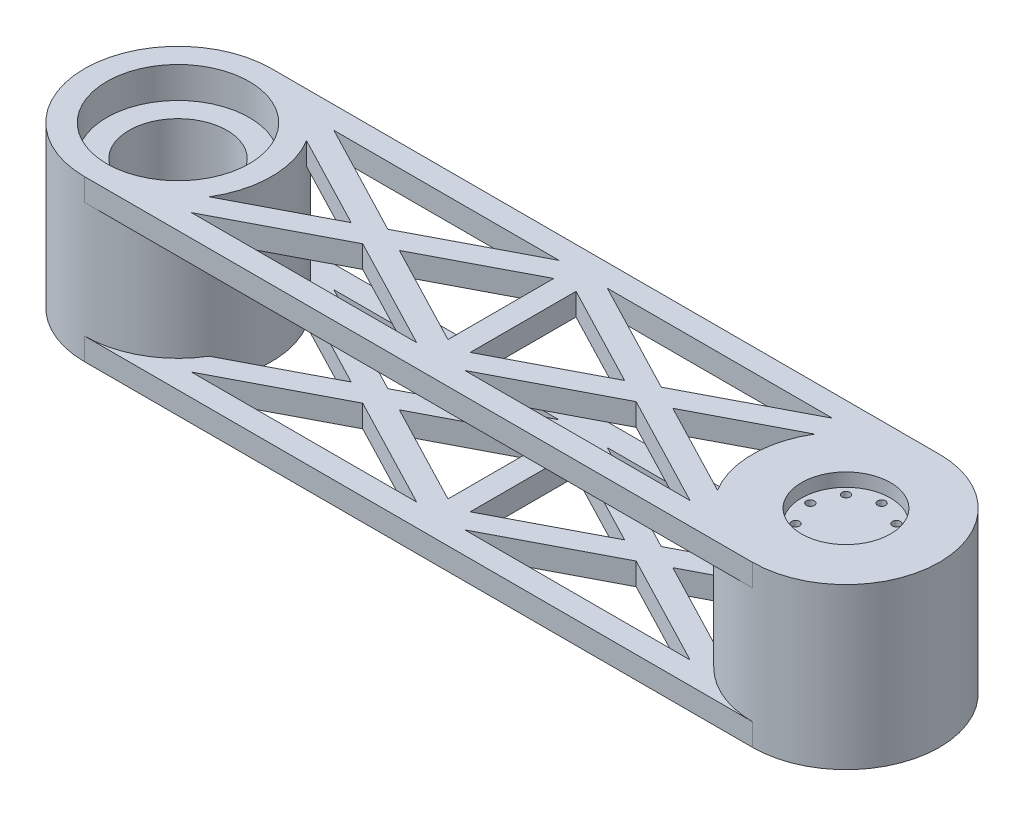
SolidWorks part; units mm, degrees
ref_plane "정면" through (0, 0, 0) normal (0, 0, 1) x (1, 0, 0)
ref_plane "윗면" through (0, 0, 0) normal (0, 1, 0) x (1, 0, 0)
ref_plane "우측면" through (0, 0, 0) normal (1, 0, 0) x (0, 0, -1)
sketch "스케치1" plane through (0, 0, 0) normal (0, 1, 0) x (1, 0, 0)
  circle A0 centre (68.9106, -5.2941) radius 21
  circle A1 centre (-81.0894, -5.2941) radius 21
  circle A2 centre (-81.0894, -5.2941) radius 16
  circle A3 centre (68.9106, -5.2941) radius 10
  dimension "D1" = 42
  dimension "D2" = 42
  dimension "D5" = 32
  dimension "D6" = 20
  dimension "D3" = 150
  dimension "D4" = 0
extrude "보스-돌출1" add sketch "스케치1" along normal blind 36
sketch "스케치2" plane through (0, 36, 0) normal (0, 1, 0) x (1, 0, 0)
  line L0 (-81.0894, -26.2941) -> (68.9106, -26.2941)
  line L1 (-81.0894, 15.7059) -> (68.9106, 15.7059)
  line L2 (-81.0894, -21.2941) -> (68.9106, -21.2941)
  line L3 (-81.0894, 10.7059) -> (68.9106, 10.7059)
  line L4 (-81.0894, -26.2941) -> (-81.0894, -21.2941)
  line L5 (68.9106, -26.2941) -> (68.9106, -21.2941)
  line L6 (68.9106, 10.7059) -> (68.9106, 15.7059)
  line L7 (-81.0894, 10.7059) -> (-81.0894, 15.7059)
  circle A1 centre (-81.0894, -5.2941) radius 21 construction
  circle A3 centre (68.9106, -5.2941) radius 21 construction
  circle A4 centre (-81.0894, -5.2941) radius 16 construction
  dimension "D1" = 21
  dimension "D2" = 21
  dimension "D3" = 5
  dimension "D4" = 5
extrude "보스-돌출3" add sketch "스케치2" against normal blind 5
sketch "스케치3" plane through (0, 0, 0) normal (0, -1, 0) x (1, 0, 0)
  line L0 (68.9106, -15.7059) -> (-81.0894, -15.7059)
  line L1 (68.9106, 26.2941) -> (-81.0894, 26.2941)
  line L2 (68.9106, 26.2941) -> (68.9106, 21.2941)
  line L3 (68.9106, -10.7059) -> (68.9106, -15.7059)
  line L4 (68.9106, 21.2941) -> (-81.0894, 21.2941)
  line L6 (-81.0894, -10.7059) -> (68.9106, -10.7059)
  line L7 (-81.0894, 26.2941) -> (-81.0894, 21.2941)
  line L8 (-81.0894, -10.7059) -> (-81.0894, -15.7059)
  circle A0 centre (68.9106, 5.2941) radius 21 construction
  circle A1 centre (-81.0894, 5.2941) radius 21 construction
  circle A3 centre (-81.0894, 5.2941) radius 16 construction
extrude "보스-돌출4" add sketch "스케치3" against normal blind 5
sketch "스케치4" plane through (0, 0, 0) normal (0, -1, 0) x (1, 0, 0)
  line L0 (-6.0894, 21.2941) -> (-6.0894, -10.7059) construction
  line L1 (-67.488, 21.2941) -> (55.3091, 21.2941) construction
  line L2 (55.3091, -10.7059) -> (-67.488, -10.7059) construction
  line L3 (-6.0894, -10.7059) -> (55.3091, 21.2941) construction
  line L4 (-36.7887, 8.1132) -> (-7.2449, 23.511)
  line L5 (55.3091, -10.7059) -> (-6.0894, 21.2941) construction
  line L6 (-67.488, -10.7059) -> (-6.0894, 21.2941) construction
  line L7 (-67.488, 21.2941) -> (-6.0894, -10.7059) construction
  line L8 (-6.0894, 21.2941) -> (-7.2449, 23.511)
  line L9 (-4.934, -12.9229) -> (24.6098, 2.4749)
  line L10 (56.4646, -8.489) -> (30.019, 5.2941)
  line L11 (-66.3325, -12.9229) -> (-36.7887, 2.4749)
  line L12 (-68.6434, 19.0771) -> (-42.1978, 5.2941)
  line L13 (-31.3795, 5.2941) -> (-8.5894, -6.5838)
  line L14 (54.1537, -12.9229) -> (24.6098, 2.4749)
  line L15 (-68.6434, -8.489) -> (-42.1978, 5.2941)
  line L16 (-66.3325, 23.511) -> (-36.7887, 8.1132)
  line L17 (-68.6434, 19.0771) -> (-66.3325, 23.511)
  line L18 (-68.6434, -8.489) -> (-66.3325, -12.9229)
  line L19 (-36.7887, 2.4749) -> (-7.2449, -12.9229)
  line L20 (-6.0894, 21.2941) -> (-4.934, 23.511)
  line L21 (-68.6434, -8.489) -> (-7.2449, 23.511) construction
  line L22 (54.1537, -12.9229) -> (56.4646, -8.489)
  line L23 (-7.2449, -12.9229) -> (-4.934, -12.9229)
  line L24 (54.1537, 23.511) -> (56.4646, 19.0771)
  line L26 (-3.5894, -6.5838) -> (19.2007, 5.2941)
  line L27 (-66.3325, 23.511) -> (-4.934, -8.489) construction
  line L32 (24.6098, 8.1132) -> (54.1537, 23.511)
  line L33 (-31.3795, 5.2941) -> (-8.5894, 17.1719)
  line L34 (19.2007, 5.2941) -> (-3.5894, 17.1719)
  line L35 (30.019, 5.2941) -> (56.4646, 19.0771)
  line L36 (54.1537, -12.9229) -> (-7.2449, 19.0771) construction
  line L37 (24.6098, 8.1132) -> (-4.934, 23.511)
  line L38 (-4.934, -12.9229) -> (56.4646, 19.0771) construction
  line L39 (-8.5894, 17.1719) -> (-8.5894, -6.5838)
  line L40 (56.4646, -8.489) -> (-4.934, 23.511) construction
  line L41 (-68.6434, 19.0771) -> (-7.2449, -12.9229) construction
  line L42 (-66.3325, -12.9229) -> (-4.934, 19.0771) construction
  line L43 (-3.5894, 17.1719) -> (-3.5894, -6.5838)
  arc A0 (-67.488, -10.7059) -> (-67.488, 21.2941) centre (-81.0894, 5.2941) ccw construction
  point P15 (-6.0894, 5.2941)
  point P17 (-8.5894, 21.2941)
  point P18 (-8.5894, -10.7059)
  point P19 (-3.5894, 21.2941)
  point P20 (-3.5894, -10.7059)
  point P29 (-7.2449, -8.489)
  dimension "D3" = 2.5
  dimension "D4" = 2.5
extrude "보스-돌출5" add sketch "스케치4" against normal blind 5
sketch "스케치7" plane through (0, 36, 0) normal (0, 1, 0) x (1, 0, 0)
  circle A0 centre (68.9106, -5.2941) radius 16
extrude "보스-돌출7" add sketch "스케치7" against normal blind 30 from offset 3 offset against normal yes
sketch "스케치8" plane through (0, 33, 0) normal (0, 1, 0) x (1, 0, 0)
  line L0 (68.9106, 2.7059) -> (68.9106, -13.2941) construction
  line L1 (68.9106, -5.2941) -> (74.5674, 0.3628) construction
  line L2 (60.9106, -5.2941) -> (76.9106, -5.2941) construction
  line L3 (68.9106, -5.2941) -> (63.2537, 0.3628) construction
  line L4 (63.2537, 0.3628) -> (74.5674, -10.9509) construction
  line L5 (68.9106, -5.2941) -> (63.2537, -10.9509) construction
  circle A0 centre (68.9106, -5.2941) radius 8 construction
  circle A1 centre (76.9106, -5.2941) radius 0.9
  circle A2 centre (68.9106, 2.7059) radius 0.9
  circle A3 centre (74.5674, 0.3628) radius 0.9
  circle A4 centre (63.2537, 0.3628) radius 0.9
  circle A5 centre (60.9106, -5.2941) radius 0.9
  circle A6 centre (68.9106, -13.2941) radius 0.9
  circle A7 centre (63.2537, -10.9509) radius 0.9
  circle A8 centre (74.5674, -10.9509) radius 0.9
  dimension "D4" = 1.8
  dimension "D5" = 1.8
  dimension "D6" = 1.8
extrude "컷-돌출1" cut sketch "스케치8" against normal blind 8
ref_plane "평면1" through (0, 18, 0) normal (0, 1, 0) x (1, 0, 0)
mirror "대칭 복사1" about plane through (0, 18, 0) normal (0, 1, 0) of "컷-돌출1"
mirror "대칭 복사2" about plane through (0, 18, 0) normal (0, 1, 0) of "보스-돌출5"
sketch "스케치9" plane through (0, 36, 0) normal (0, 1, 0) x (1, 0, 0)
  circle A0 centre (-81.0894, -5.2941) radius 16
  dimension "D1" = 32
sketch "스케치10" plane through (0, 36, 0) normal (0, 1, 0) x (1, 0, 0)
  circle A0 centre (-81.0894, -5.2941) radius 18.2432
  circle A1 centre (-81.0894, -5.2941) radius 11
  dimension "D1" = 22
extrude "보스-돌출8" add sketch "스케치10" against normal blind 22 from offset 7 offset against normal yes
